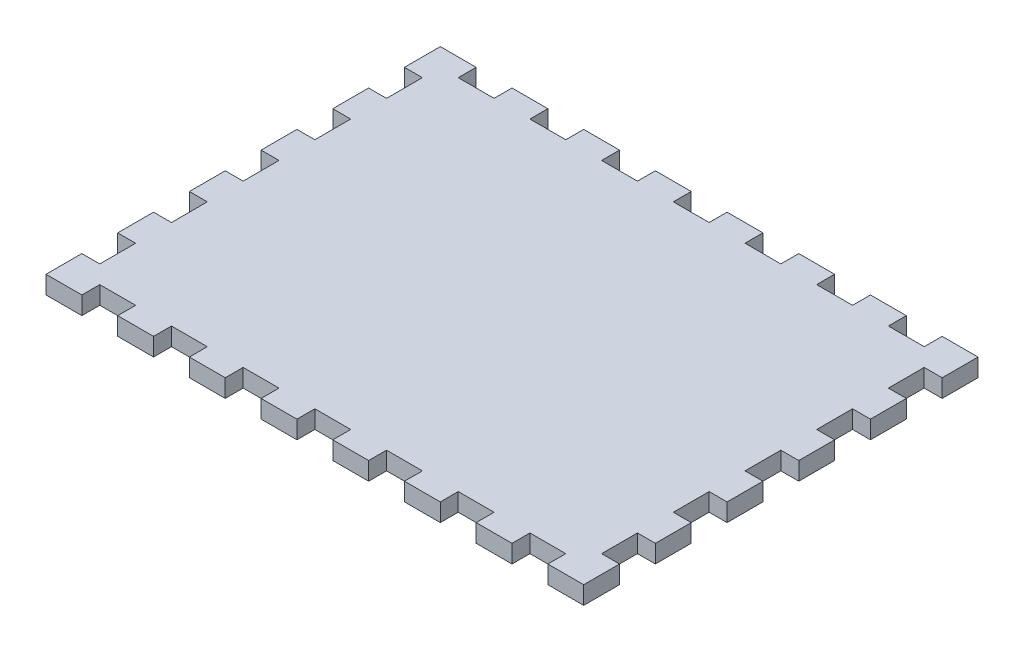
SolidWorks part; units mm, degrees
ref_plane "Front Plane" through (0, 0, 0) normal (0, 0, 1) x (1, 0, 0)
ref_plane "Top Plane" through (0, 0, 0) normal (0, 1, 0) x (1, 0, 0)
ref_plane "Right Plane" through (0, 0, 0) normal (1, 0, 0) x (0, 0, -1)
sketch "Sketch1" plane through (0, 0, 0) normal (0, 1, 0) x (1, 0, 0)
  line L1 (-95.25, -69.85) -> (95.25, -69.85)
  line L2 (-95.25, -69.85) -> (-95.25, 69.85)
  line L3 (-95.25, 69.85) -> (95.25, 69.85)
  line L4 (95.25, -69.85) -> (95.25, 69.85)
  line L5 (-95.25, -69.85) -> (95.25, 69.85) construction
  line L6 (-95.25, 69.85) -> (95.25, -69.85) construction
  point P0 (0, 0)
  dimension "D1" = 190.5
  dimension "D2" = 139.7
extrude "Boss-Extrude1" add sketch "Sketch1" along normal blind 6.35
sketch "Sketch2" plane through (0, 6.35, 0) normal (0, 1, 0) x (1, 0, 0)
  line L0 (95.25, 69.85) -> (-95.25, 69.85) construction
  line L2 (-6.35, 76.2) -> (6.35, 76.2)
  line L3 (-6.35, 76.2) -> (-6.35, 63.5)
  line L4 (-6.35, 63.5) -> (6.35, 63.5)
  line L5 (6.35, 76.2) -> (6.35, 63.5)
  line L6 (-6.35, 76.2) -> (6.35, 63.5) construction
  line L7 (-6.35, 63.5) -> (6.35, 76.2) construction
  point P0 (0, 69.85)
  point P1 (0, 69.85)
  dimension "D1" = 12.7
  dimension "D2" = 12.7
extrude "Cut-Extrude1" cut sketch "Sketch2" against normal up to next
pattern_linear "LPattern1" count 4 spacing 25.4 along (-1, 0, 0) of "Cut-Extrude1"
pattern_linear "LPattern2" count 4 spacing 25.4 along (1, 0, 0) of "Cut-Extrude1"
ref_axis "Axis1" through (0, 0, 0) along (0, 1, 0)
pattern_circular "CirPattern1" count 2 over 360 about axis through (0, 0, 0) along (0, 1, 0) of "Cut-Extrude1", "LPattern1", "LPattern2"
sketch "Sketch3" plane through (0, 6.35, 0) normal (0, 1, 0) x (1, 0, 0)
  line L0 (-95.25, 69.85) -> (-95.25, -69.85) construction
  line L2 (-101.6, -6.35) -> (-88.9, -6.35)
  line L3 (-101.6, -6.35) -> (-101.6, 6.35)
  line L4 (-101.6, 6.35) -> (-88.9, 6.35)
  line L5 (-88.9, -6.35) -> (-88.9, 6.35)
  line L6 (-101.6, -6.35) -> (-88.9, 6.35) construction
  line L7 (-101.6, 6.35) -> (-88.9, -6.35) construction
  point P0 (-95.25, 0)
  point P1 (-95.25, 0)
  dimension "D1" = 12.7
  dimension "D2" = 12.7
extrude "Cut-Extrude2" cut sketch "Sketch3" against normal up to next
pattern_linear "LPattern3" count 3 spacing 25.4 along (0, 0, -1) of "Cut-Extrude2"
pattern_linear "LPattern4" count 3 spacing 25.4 along (0, 0, 1) of "Cut-Extrude2"
pattern_circular "CirPattern2" count 2 over 360 about axis through (0, 0, 0) along (0, 1, 0) of "Cut-Extrude2", "LPattern3", "LPattern4"
